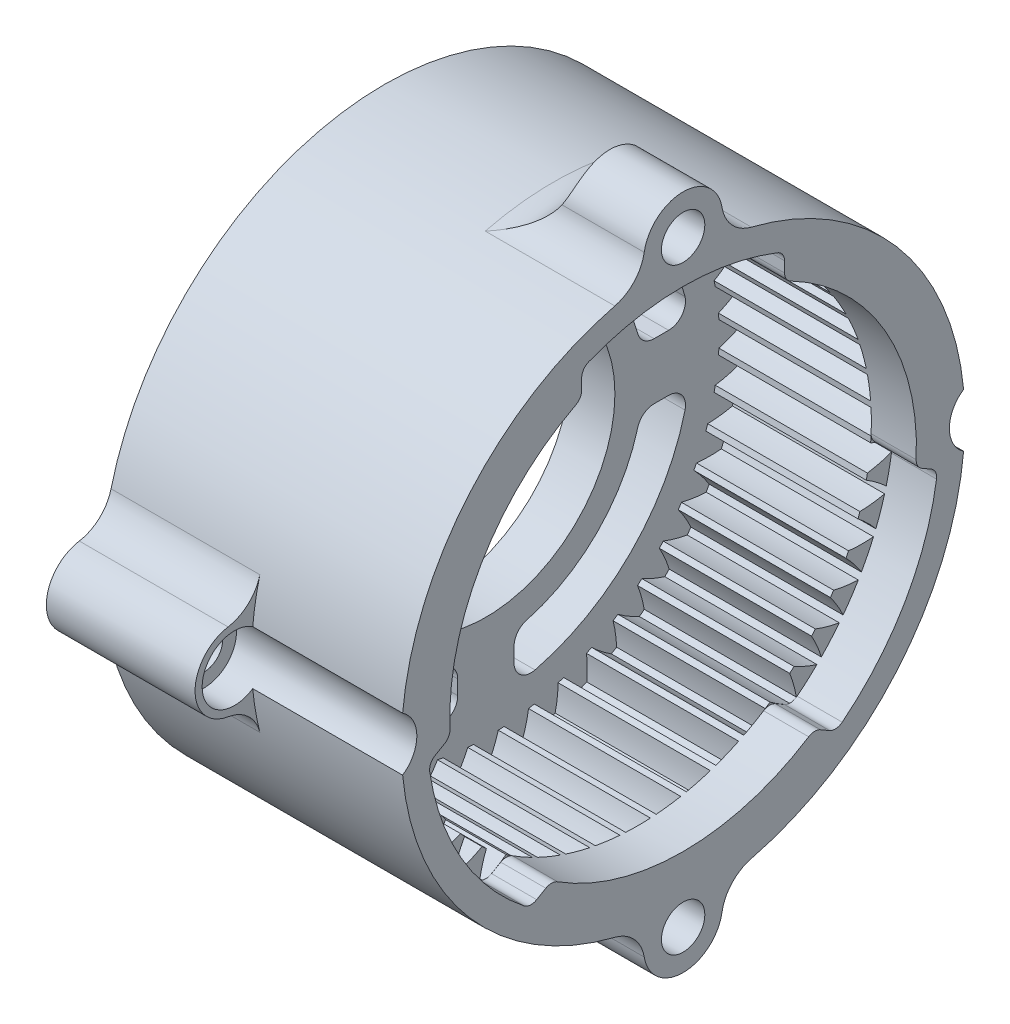
SolidWorks part; units mm, degrees
other "Markup1"
sketch "Sketch14" plane through (17.5, -30, 30) normal (0.8542, -0.3132, 0.4151) x (-0.0246, -0.8217, -0.5694)
other "Markup2"
sketch "Sketch16" plane through (17.5, -30, 30) normal (0.4906, -0.845, 0.2126) x (0.2236, -0.1138, -0.968)
ref_plane "Plane1" through (0, 0, 0) normal (0, 0, 1) x (1, 0, 0)
ref_plane "Plane2" through (0, 0, 0) normal (0, 1, 0) x (1, 0, 0)
ref_plane "Plane3" through (0, 0, 0) normal (1, 0, 0) x (0, 0, -1)
other "Configuration Table"
sketch "HoldingSke" plane through (0, 0, 0) normal (0, 1, 0) x (1, 0, 0)
  line L0 (0, 0) -> (0.7435, -0.8257)
  line L1 (-15, 0) -> (100, 0) construction
  line L2 (0, 0) -> (-2.1039, 2.3779)
  line L3 (0, 0) -> (-11.863, 4.5341)
  line L4 (0, 0) -> (5.7786, 6.4178)
  line L5 (0, 0) -> (-23.7986, -8.8762)
  line L6 (0, 0) -> (-10.5278, -7.1032)
  line L7 (-2.1039, 2.3779) -> (3.3635, 27.1825)
  line L8 (-76.2, 3.2779) -> (-54.61, 3.2779)
  line L9 (-71.009, 38.7566) -> (-53.1078, 45.2721)
  line L10 (-76.2, 71.12) -> (104.1128, 71.12)
  line L11 (0, 0) -> (-12, 0)
  line L12 (-76.2, 101.6) -> (-76.166, 101.6)
  line L13 (24.9733, 27.94) -> (52.9518, 28.4284)
  line L14 (24.9733, 27.94) -> (24.9743, 27.94)
  line L15 (24.9733, 27.94) -> (100.4006, 29.5858)
  circle A0 centre (0, 0) radius 25
  circle A1 centre (0, 0) radius 12.7
  circle A2 centre (0, 0) radius 12.7
  dimension "MHD" = 25.4
  dimension "Hub_dia" = 25.4
  dimension "Diameter" = 50
  dimension "Num_teeth" = 48
  dimension "Pitch" = 1.1111
  dimension "Overall_len" = 25.4
  dimension "Show_teeth" = 48
  dimension "Thickness" = 12.7
  dimension "OAL" = 25.4001
  dimension "T_dim" = 21.59
  dimension "Ap" = 20
  dimension "H" = 19.05
  dimension "Pitch_radius" = 180.3128
  dimension "Width" = 12
  dimension "Backlash" = 0.034
  dimension "Addendum_fac" = 1
  dimension "Dedendum_fac" = 1.25
  dimension "Clearance_fac" = 0.25
  dimension "Dedendum_add" = 0.001
  dimension "Module" = 0.9
sketch "BasProSke" plane through (0, 0, 0) normal (0, 1, 0) x (1, 0, 0)
  line L0 (-10, 0) -> (60, 0) construction
  line L1 (0, 20.7) -> (0, 25)
  line L2 (0, 20.7) -> (12, 20.7)
  line L3 (12, 20.7) -> (12, 25)
  line L4 (12, 25) -> (0, 25)
  dimension "Diameter" = 50
  dimension "Thickness" = 12
  dimension "Inside_diameter" = 41.4
revolve "Base-Revolve" add sketch "BasProSke" angle 360 about L0
sketch "TooCutSke" plane through (0, 0, 0) normal (1, 0, 0) x (0, 0, -1)
  line L3 (0.7917, 21.5855) -> (0.7917, 53.6633) construction
  line L4 (0, 0) -> (0, 59.563) construction
  line L5 (0, 0) -> (-4.4688, 68.1812) construction
  line L6 (-9.2845, 17.6983) -> (36.567, 20.7035) construction
  circle A0 centre (0, 0) radius 21.6 construction
  circle A1 centre (0, 0) radius 22.726 construction
  circle A2 centre (0, 0) radius 18.2676 construction
  circle A3 centre (0, 0) radius 20.6746 construction
  arc A4 (1.1058, 20.645) -> (0.2748, 22.7243) centre (-9.2845, 17.6983) ccw
  arc A5 (1.1058, 20.645) -> (-1.1058, 20.645) centre (0, 0) ccw
  arc A6 (0.2748, 22.7243) -> (-0.2748, 22.7243) centre (0, 0) ccw
  arc A7 (-0.2748, 22.7243) -> (-1.1058, 20.645) centre (9.2845, 17.6983) ccw
  dimension "Pitch_dia" = 43.2
  dimension "Base_dia" = 36.5352
  dimension "Root_dia" = 45.452
  dimension "Overcut_dia" = 41.3492
  dimension "Flank_rad" = 10.8
  dimension "Half_ang" = 3.75
  dimension "Half_CT" = 0.7917
extrude "ToothCut" cut sketch "TooCutSke" along normal through all
fillet "Breaks" [suppressed] radius 0.09
fillet "RootFillets" [suppressed] radius 0.226
pattern_circular "TeethCuts" count 48 every 7.5 about axis through (-10, 0, 0) along (1, 0, 0) of "RootFillets", "Breaks", "ToothCut"
sketch "Sketch1" plane through (0, 0, 0) normal (-1, 0, 0) x (0, 0, 1)
  circle A0 centre (0, 0) radius 25
  circle A1 centre (0, 0) radius 25 construction
  circle A2 centre (0, 0) radius 11.45
  dimension "D1" = 22.9
extrude "Boss-Extrude1" add sketch "Sketch1" along normal blind 9
ref_plane "Plane4" through (1.5, 0, 0) normal (-1, 0, 0) x (0, 0, 1)
sketch "Sketch2" plane through (1.5, 0, 0) normal (-1, 0, 0) x (0, 0, 1)
  line L0 (-26.5, 0) -> (0, 0) construction
  line L1 (0, 11.45) -> (0, -11.45) construction
  line L2 (-26.5, 3.5) -> (-24.7538, 3.5)
  line L3 (-26.5, -3.5) -> (-24.7538, -3.5)
  line L4 (26.5, 3.5) -> (24.7538, 3.5)
  line L5 (26.5, -3.5) -> (24.7538, -3.5)
  arc A0 (-26.5, 3.5) -> (-26.5, -3.5) centre (-26.5, 0) ccw
  circle A1 centre (0, 0) radius 25 construction
  arc A2 (-24.7538, 3.5) -> (-24.7538, -3.5) centre (0, 0) ccw
  circle A3 centre (0, 0) radius 11.45 construction
  arc A4 (24.7538, 3.5) -> (24.7538, -3.5) centre (0, 0) cw
  arc A5 (26.5, 3.5) -> (26.5, -3.5) centre (26.5, 0) cw
  point P12 (0, 0)
  dimension "D2" = 7
  dimension "D1" = 26.5
extrude "Boss-Extrude2" add sketch "Sketch2" along normal up to surface (10.5 mm away) up to face at (-9, 0, 25)
sketch "Sketch3" plane through (1.5, 0, 0) normal (1, 0, 0) x (0, 0, -1)
  circle A0 centre (-26.5, 0) radius 1.65
  circle A1 centre (26.5, 0) radius 1.65
  arc A2 (26.5, -3.5) -> (26.5, 3.5) centre (26.5, 0) ccw construction
  arc A4 (-26.5, 3.5) -> (-26.5, -3.5) centre (-26.5, 0) ccw construction
  dimension "D1" = 3.3
extrude "Cut-Extrude1" cut sketch "Sketch3" against normal up to surface (10.5 mm away) up to face at (-9, 0, 0)
sketch "Sketch4" plane through (1.5, 0, 0) normal (1, 0, 0) x (0, 0, -1)
  line L0 (0, 11.45) -> (0, -11.45) construction
  circle A1 centre (26.5, 0) radius 2.875
  arc A2 (26.5, -3.5) -> (26.5, 3.5) centre (26.5, 0) ccw construction
  circle A3 centre (0, 0) radius 11.45 construction
  circle A4 centre (-26.5, 0) radius 2.875
  point P12 (0, 0)
  dimension "D1" = 5.75
extrude "Cut-Extrude2" cut sketch "Sketch4" along normal through all
sketch "Sketch5" plane through (1.5, 0, 0) normal (1, 0, 0) x (0, 0, -1)
  line L0 (0, 11.45) -> (0, -11.45) construction
  line L1 (-24.7538, -3.5) -> (-26.5, -3.5)
  line L2 (24.7538, -3.5) -> (26.5, -3.5)
  line L3 (26.5, 3.5) -> (24.7538, 3.5)
  line L4 (24.7538, -3.5) -> (26.5, -3.5)
  line L5 (26.5, 3.5) -> (24.7538, 3.5)
  line L6 (-26.5, 3.5) -> (-24.7538, 3.5)
  arc A0 (24.8865, -2.3795) -> (24.8865, 2.3795) centre (26.5, 0) ccw
  arc A1 (26.5, -3.5) -> (26.5, 3.5) centre (26.5, 0) ccw construction
  circle A3 centre (0, 0) radius 11.45 construction
  arc A4 (-24.8865, -2.3795) -> (-24.8865, 2.3795) centre (-26.5, 0) cw
  arc A5 (-24.7538, -3.5) -> (-24.8865, -2.3795) centre (0, 0) cw
  arc A6 (-26.5, -3.5) -> (-26.5, 3.5) centre (-26.5, 0) cw
  arc A7 (24.8865, 2.3795) -> (24.7538, 3.5) centre (0, 0) ccw
  arc A10 (26.5, -3.5) -> (26.5, 3.5) centre (26.5, 0) ccw
  arc A14 (26.5, -3.5) -> (26.5, 3.5) centre (26.5, 0) ccw
  arc A15 (-24.8865, 2.3795) -> (-24.7538, 3.5) centre (0, 0) cw
  arc A19 (24.8865, 2.3795) -> (24.7538, 3.5) centre (0, 0) ccw
  arc A21 (24.8865, 2.3795) -> (24.8865, -2.3795) centre (26.5, 0) ccw
  arc A23 (24.7538, -3.5) -> (24.8865, -2.3795) centre (0, 0) ccw
  arc A24 (24.7538, -3.5) -> (24.8865, -2.3795) centre (0, 0) ccw
  point P19 (0, 0)
  dimension "D1" = 2.875
  dimension "D2" = 0
extrude "Boss-Extrude3" add sketch "Sketch5" along normal blind 2.7
sketch "Sketch8" plane through (-9, 0, 0) normal (-1, 0, 0) x (0, 0, 1)
  circle A0 centre (0, 0) radius 20.7
  arc A1 (20.3506, 3.7871) -> (20.2508, 4.289) centre (0, 0) ccw construction
extrude "Cut-Extrude4" cut sketch "Sketch8" against normal blind 5 and the other way through all
fillet "Fillet1" radius 3.5 4 edges at (-2.4, 3.5, -24.7538) (-2.4, -3.5, -24.7538) (-2.4, -3.5, 24.7538) (-2.4, 3.5, 24.7538)
sketch "Sketch15" plane through (12, 0, 0) normal (1, 0, 0) x (0, 0, -1)
  arc A12 (24.8865, 2.3795) -> (24.8865, -2.3795) centre (26.5, 0) ccw construction
  arc A13 (24.8865, 2.3795) -> (-24.8865, 2.3795) centre (0, 0) ccw construction
  arc A14 (-24.8865, -2.3795) -> (-24.8865, 2.3795) centre (-26.5, 0) ccw construction
  arc A15 (-24.8865, -2.3795) -> (24.8865, -2.3795) centre (0, 0) ccw construction
  arc A16 (-3.2385, -22.4941) -> (-2.6937, -22.5658) centre (0, 0) ccw construction
  arc A17 (-2.6937, -22.5658) -> (-1.6091, -20.6374) centre (-11.5151, -16.335) ccw construction
  arc A18 (-1.6091, -20.6374) -> (-1.0984, -20.6708) centre (0, 0) ccw construction
  arc A19 (-1.0984, -20.6708) -> (-0.2748, -22.7243) centre (9.2845, -17.6983) ccw construction
  arc A20 (-0.2748, -22.7243) -> (0.2748, -22.7243) centre (0, 0) ccw construction
  arc A21 (0.2748, -22.7243) -> (1.0984, -20.6708) centre (-9.2845, -17.6983) ccw construction
  arc A22 (1.0984, -20.6708) -> (1.6091, -20.6374) centre (0, 0) ccw construction
  arc A23 (1.6091, -20.6374) -> (2.6937, -22.5658) centre (11.5151, -16.335) ccw construction
  arc A24 (2.6937, -22.5658) -> (3.2385, -22.4941) centre (0, 0) ccw construction
  arc A25 (3.2385, -22.4941) -> (3.7871, -20.3506) centre (-6.8949, -18.7587) ccw construction
  arc A26 (3.7871, -20.3506) -> (4.289, -20.2508) centre (0, 0) ccw construction
  arc A27 (4.289, -20.2508) -> (5.6161, -22.0211) centre (13.5488, -14.6922) ccw construction
  arc A28 (5.6161, -22.0211) -> (6.1469, -21.8789) centre (0, 0) ccw construction
  arc A29 (6.1469, -21.8789) -> (6.411, -19.6822) centre (-4.3874, -19.4982) ccw construction
  arc A30 (6.411, -19.6822) -> (6.8956, -19.5177) centre (0, 0) ccw construction
  arc A31 (6.8956, -19.5177) -> (8.4424, -21.0997) centre (15.3506, -12.7981) ccw construction
  arc A32 (8.4424, -21.0997) -> (8.9501, -20.8894) centre (0, 0) ccw construction
  arc A33 (8.9501, -20.8894) -> (8.9252, -18.677) centre (-1.8049, -19.9041) ccw construction
  arc A34 (8.9252, -18.677) -> (9.3842, -18.4507) centre (0, 0) ccw construction
  arc A35 (9.3842, -18.4507) -> (11.1242, -19.8172) centre (16.8897, -10.6849) ccw construction
  arc A36 (11.1242, -19.8172) -> (11.6001, -19.5425) centre (0, 0) ccw construction
  arc A37 (11.6001, -19.5425) -> (11.2867, -17.3523) centre (0.8086, -19.9694) ccw construction
  arc A38 (11.2867, -17.3523) -> (11.7122, -17.0679) centre (0, 0) ccw construction
  arc A39 (11.7122, -17.0679) -> (13.6157, -18.1957) centre (18.1399, -8.389) ccw construction
  arc A40 (13.6157, -18.1957) -> (14.0517, -17.8612) centre (0, 0) ccw construction
  arc A41 (14.0517, -17.8612) -> (13.455, -15.7306) centre (3.4082, -19.693) ccw construction
  arc A42 (13.455, -15.7306) -> (13.8398, -15.3932) centre (0, 0) ccw construction
  arc A43 (13.8398, -15.3932) -> (15.8742, -16.2628) centre (19.0797, -5.9495) ccw construction
  arc A44 (15.8742, -16.2628) -> (16.2628, -15.8742) centre (0, 0) ccw construction
  arc A45 (16.2628, -15.8742) -> (15.3932, -13.8398) centre (5.9495, -19.0797) ccw construction
  arc A46 (15.3932, -13.8398) -> (15.7306, -13.455) centre (0, 0) ccw construction
  arc A47 (15.7306, -13.455) -> (17.8612, -14.0517) centre (19.693, -3.4082) ccw construction
  arc A48 (17.8612, -14.0517) -> (18.1957, -13.6157) centre (0, 0) ccw construction
  arc A49 (18.1957, -13.6157) -> (17.0679, -11.7122) centre (8.389, -18.1399) ccw construction
  arc A50 (17.0679, -11.7122) -> (17.3523, -11.2867) centre (0, 0) ccw construction
  arc A51 (17.3523, -11.2867) -> (19.5425, -11.6001) centre (19.9694, -0.8086) ccw construction
  arc A52 (19.5425, -11.6001) -> (19.8172, -11.1242) centre (0, 0) ccw construction
  arc A53 (19.8172, -11.1242) -> (18.4507, -9.3842) centre (10.6849, -16.8897) ccw construction
  arc A54 (18.4507, -9.3842) -> (18.677, -8.9252) centre (0, 0) ccw construction
  arc A55 (18.677, -8.9252) -> (20.8894, -8.9501) centre (19.9041, 1.8049) ccw construction
  arc A56 (20.8894, -8.9501) -> (21.0997, -8.4424) centre (0, 0) ccw construction
  arc A57 (21.0997, -8.4424) -> (19.5177, -6.8956) centre (12.7981, -15.3506) ccw construction
  arc A58 (19.5177, -6.8956) -> (19.6822, -6.411) centre (0, 0) ccw construction
  arc A59 (19.6822, -6.411) -> (21.8789, -6.1469) centre (19.4982, 4.3874) ccw construction
  arc A60 (21.8789, -6.1469) -> (22.0211, -5.6161) centre (0, 0) ccw construction
  arc A61 (22.0211, -5.6161) -> (20.2508, -4.289) centre (14.6922, -13.5488) ccw construction
  arc A62 (20.2508, -4.289) -> (20.3506, -3.7871) centre (0, 0) ccw construction
  arc A63 (20.3506, -3.7871) -> (22.4941, -3.2385) centre (18.7587, 6.8949) ccw construction
  arc A64 (22.4941, -3.2385) -> (22.5658, -2.6937) centre (0, 0) ccw construction
  arc A65 (22.5658, -2.6937) -> (20.6374, -1.6091) centre (16.335, -11.5151) ccw construction
  arc A66 (20.6374, -1.6091) -> (20.6708, -1.0984) centre (0, 0) ccw construction
  arc A67 (20.6708, -1.0984) -> (22.7243, -0.2748) centre (17.6983, 9.2845) ccw construction
  arc A68 (22.7243, -0.2748) -> (22.7243, 0.2748) centre (0, 0) ccw construction
  arc A69 (22.7243, 0.2748) -> (20.6708, 1.0984) centre (17.6983, -9.2845) ccw construction
  arc A70 (20.6708, 1.0984) -> (20.6374, 1.6091) centre (0, 0) ccw construction
  arc A71 (20.6374, 1.6091) -> (22.5658, 2.6937) centre (16.335, 11.5151) ccw construction
  arc A72 (22.5658, 2.6937) -> (22.4941, 3.2385) centre (0, 0) ccw construction
  arc A73 (22.4941, 3.2385) -> (20.3506, 3.7871) centre (18.7587, -6.8949) ccw construction
  arc A74 (20.3506, 3.7871) -> (20.2508, 4.289) centre (0, 0) ccw construction
  arc A75 (20.2508, 4.289) -> (22.0211, 5.6161) centre (14.6922, 13.5488) ccw construction
  arc A76 (22.0211, 5.6161) -> (21.8789, 6.1469) centre (0, 0) ccw construction
  arc A77 (21.8789, 6.1469) -> (19.6822, 6.411) centre (19.4982, -4.3874) ccw construction
  arc A78 (19.6822, 6.411) -> (19.5177, 6.8956) centre (0, 0) ccw construction
  arc A79 (19.5177, 6.8956) -> (21.0997, 8.4424) centre (12.7981, 15.3506) ccw construction
  arc A80 (21.0997, 8.4424) -> (20.8894, 8.9501) centre (0, 0) ccw construction
  arc A81 (20.8894, 8.9501) -> (18.677, 8.9252) centre (19.9041, -1.8049) ccw construction
  arc A82 (18.677, 8.9252) -> (18.4507, 9.3842) centre (0, 0) ccw construction
  arc A83 (18.4507, 9.3842) -> (19.8172, 11.1242) centre (10.6849, 16.8897) ccw construction
  arc A84 (19.8172, 11.1242) -> (19.5425, 11.6001) centre (0, 0) ccw construction
  arc A85 (19.5425, 11.6001) -> (17.3523, 11.2867) centre (19.9694, 0.8086) ccw construction
  arc A86 (17.3523, 11.2867) -> (17.0679, 11.7122) centre (0, 0) ccw construction
  arc A87 (17.0679, 11.7122) -> (18.1957, 13.6157) centre (8.389, 18.1399) ccw construction
  arc A88 (18.1957, 13.6157) -> (17.8612, 14.0517) centre (0, 0) ccw construction
  arc A89 (17.8612, 14.0517) -> (15.7306, 13.455) centre (19.693, 3.4082) ccw construction
  arc A90 (15.7306, 13.455) -> (15.3932, 13.8398) centre (0, 0) ccw construction
  arc A91 (15.3932, 13.8398) -> (16.2628, 15.8742) centre (5.9495, 19.0797) ccw construction
  arc A92 (16.2628, 15.8742) -> (15.8742, 16.2628) centre (0, 0) ccw construction
  arc A93 (15.8742, 16.2628) -> (13.8398, 15.3932) centre (19.0797, 5.9495) ccw construction
  arc A94 (13.8398, 15.3932) -> (13.455, 15.7306) centre (0, 0) ccw construction
  arc A95 (13.455, 15.7306) -> (14.0517, 17.8612) centre (3.4082, 19.693) ccw construction
  arc A96 (14.0517, 17.8612) -> (13.6157, 18.1957) centre (0, 0) ccw construction
  arc A97 (13.6157, 18.1957) -> (11.7122, 17.0679) centre (18.1399, 8.389) ccw construction
  arc A98 (11.7122, 17.0679) -> (11.2867, 17.3523) centre (0, 0) ccw construction
  arc A99 (11.2867, 17.3523) -> (11.6001, 19.5425) centre (0.8086, 19.9694) ccw construction
  arc A100 (11.6001, 19.5425) -> (11.1242, 19.8172) centre (0, 0) ccw construction
  arc A101 (11.1242, 19.8172) -> (9.3842, 18.4507) centre (16.8897, 10.6849) ccw construction
  arc A102 (9.3842, 18.4507) -> (8.9252, 18.677) centre (0, 0) ccw construction
  arc A103 (8.9252, 18.677) -> (8.9501, 20.8894) centre (-1.8049, 19.9041) ccw construction
  arc A104 (8.9501, 20.8894) -> (8.4424, 21.0997) centre (0, 0) ccw construction
  arc A105 (8.4424, 21.0997) -> (6.8956, 19.5177) centre (15.3506, 12.7981) ccw construction
  arc A106 (6.8956, 19.5177) -> (6.411, 19.6822) centre (0, 0) ccw construction
  arc A107 (6.411, 19.6822) -> (6.1469, 21.8789) centre (-4.3874, 19.4982) ccw construction
  arc A108 (6.1469, 21.8789) -> (5.6161, 22.0211) centre (0, 0) ccw construction
  arc A109 (5.6161, 22.0211) -> (4.289, 20.2508) centre (13.5488, 14.6922) ccw construction
  arc A110 (4.289, 20.2508) -> (3.7871, 20.3506) centre (0, 0) ccw construction
  arc A111 (3.7871, 20.3506) -> (3.2385, 22.4941) centre (-6.8949, 18.7587) ccw construction
  arc A112 (3.2385, 22.4941) -> (2.6937, 22.5658) centre (0, 0) ccw construction
  arc A113 (2.6937, 22.5658) -> (1.6091, 20.6374) centre (11.5151, 16.335) ccw construction
  arc A114 (1.6091, 20.6374) -> (1.0984, 20.6708) centre (0, 0) ccw construction
  arc A115 (1.0984, 20.6708) -> (0.2748, 22.7243) centre (-9.2845, 17.6983) ccw construction
  arc A116 (0.2748, 22.7243) -> (-0.2748, 22.7243) centre (0, 0) ccw construction
  arc A117 (-0.2748, 22.7243) -> (-1.0984, 20.6708) centre (9.2845, 17.6983) ccw construction
  arc A118 (-1.0984, 20.6708) -> (-1.6091, 20.6374) centre (0, 0) ccw construction
  arc A119 (-1.6091, 20.6374) -> (-2.6937, 22.5658) centre (-11.5151, 16.335) ccw construction
  arc A120 (-2.6937, 22.5658) -> (-3.2385, 22.4941) centre (0, 0) ccw construction
  arc A121 (-3.2385, 22.4941) -> (-3.7871, 20.3506) centre (6.8949, 18.7587) ccw construction
  arc A122 (-3.7871, 20.3506) -> (-4.289, 20.2508) centre (0, 0) ccw construction
  arc A123 (-4.289, 20.2508) -> (-5.6161, 22.0211) centre (-13.5488, 14.6922) ccw construction
  arc A124 (-5.6161, 22.0211) -> (-6.1469, 21.8789) centre (0, 0) ccw construction
  arc A125 (-6.1469, 21.8789) -> (-6.411, 19.6822) centre (4.3874, 19.4982) ccw construction
  arc A126 (-6.411, 19.6822) -> (-6.8956, 19.5177) centre (0, 0) ccw construction
  arc A127 (-6.8956, 19.5177) -> (-8.4424, 21.0997) centre (-15.3506, 12.7981) ccw construction
  arc A128 (-8.4424, 21.0997) -> (-8.9501, 20.8894) centre (0, 0) ccw construction
  arc A129 (-8.9501, 20.8894) -> (-8.9252, 18.677) centre (1.8049, 19.9041) ccw construction
  arc A130 (-8.9252, 18.677) -> (-9.3842, 18.4507) centre (0, 0) ccw construction
  arc A131 (-9.3842, 18.4507) -> (-11.1242, 19.8172) centre (-16.8897, 10.6849) ccw construction
  arc A132 (-11.1242, 19.8172) -> (-11.6001, 19.5425) centre (0, 0) ccw construction
  arc A133 (-11.6001, 19.5425) -> (-11.2867, 17.3523) centre (-0.8086, 19.9694) ccw construction
  arc A134 (-11.2867, 17.3523) -> (-11.7122, 17.0679) centre (0, 0) ccw construction
  arc A135 (-11.7122, 17.0679) -> (-13.6157, 18.1957) centre (-18.1399, 8.389) ccw construction
  arc A136 (-13.6157, 18.1957) -> (-14.0517, 17.8612) centre (0, 0) ccw construction
  arc A137 (-14.0517, 17.8612) -> (-13.455, 15.7306) centre (-3.4082, 19.693) ccw construction
  arc A138 (-13.455, 15.7306) -> (-13.8398, 15.3932) centre (0, 0) ccw construction
  arc A139 (-13.8398, 15.3932) -> (-15.8742, 16.2628) centre (-19.0797, 5.9495) ccw construction
  arc A140 (-15.8742, 16.2628) -> (-16.2628, 15.8742) centre (0, 0) ccw construction
  arc A141 (-16.2628, 15.8742) -> (-15.3932, 13.8398) centre (-5.9495, 19.0797) ccw construction
  arc A142 (-15.3932, 13.8398) -> (-15.7306, 13.455) centre (0, 0) ccw construction
  arc A143 (-15.7306, 13.455) -> (-17.8612, 14.0517) centre (-19.693, 3.4082) ccw construction
  arc A144 (-17.8612, 14.0517) -> (-18.1957, 13.6157) centre (0, 0) ccw construction
  arc A145 (-18.1957, 13.6157) -> (-17.0679, 11.7122) centre (-8.389, 18.1399) ccw construction
  arc A146 (-17.0679, 11.7122) -> (-17.3523, 11.2867) centre (0, 0) ccw construction
  arc A147 (-17.3523, 11.2867) -> (-19.5425, 11.6001) centre (-19.9694, 0.8086) ccw construction
  arc A148 (-19.5425, 11.6001) -> (-19.8172, 11.1242) centre (0, 0) ccw construction
  arc A149 (-19.8172, 11.1242) -> (-18.4507, 9.3842) centre (-10.6849, 16.8897) ccw construction
  arc A150 (-18.4507, 9.3842) -> (-18.677, 8.9252) centre (0, 0) ccw construction
  arc A151 (-18.677, 8.9252) -> (-20.8894, 8.9501) centre (-19.9041, -1.8049) ccw construction
  arc A152 (-20.8894, 8.9501) -> (-21.0997, 8.4424) centre (0, 0) ccw construction
  arc A153 (-21.0997, 8.4424) -> (-19.5177, 6.8956) centre (-12.7981, 15.3506) ccw construction
  arc A154 (-19.5177, 6.8956) -> (-19.6822, 6.411) centre (0, 0) ccw construction
  arc A155 (-19.6822, 6.411) -> (-21.8789, 6.1469) centre (-19.4982, -4.3874) ccw construction
  arc A156 (-21.8789, 6.1469) -> (-22.0211, 5.6161) centre (0, 0) ccw construction
  arc A157 (-22.0211, 5.6161) -> (-20.2508, 4.289) centre (-14.6922, 13.5488) ccw construction
  arc A158 (-20.2508, 4.289) -> (-20.3506, 3.7871) centre (0, 0) ccw construction
  arc A159 (-20.3506, 3.7871) -> (-22.4941, 3.2385) centre (-18.7587, -6.8949) ccw construction
  arc A160 (-22.4941, 3.2385) -> (-22.5658, 2.6937) centre (0, 0) ccw construction
  arc A161 (-22.5658, 2.6937) -> (-20.6374, 1.6091) centre (-16.335, 11.5151) ccw construction
  arc A162 (-20.6374, 1.6091) -> (-20.6708, 1.0984) centre (0, 0) ccw construction
  arc A163 (-20.6708, 1.0984) -> (-22.7243, 0.2748) centre (-17.6983, -9.2845) ccw construction
  arc A164 (-22.7243, 0.2748) -> (-22.7243, -0.2748) centre (0, 0) ccw construction
  arc A165 (-22.7243, -0.2748) -> (-20.6708, -1.0984) centre (-17.6983, 9.2845) ccw construction
  arc A166 (-20.6708, -1.0984) -> (-20.6374, -1.6091) centre (0, 0) ccw construction
  arc A167 (-20.6374, -1.6091) -> (-22.5658, -2.6937) centre (-16.335, -11.5151) ccw construction
  arc A168 (-22.5658, -2.6937) -> (-22.4941, -3.2385) centre (0, 0) ccw construction
  arc A169 (-22.4941, -3.2385) -> (-20.3506, -3.7871) centre (-18.7587, 6.8949) ccw construction
  arc A170 (-20.3506, -3.7871) -> (-20.2508, -4.289) centre (0, 0) ccw construction
  arc A171 (-20.2508, -4.289) -> (-22.0211, -5.6161) centre (-14.6922, -13.5488) ccw construction
  arc A172 (-22.0211, -5.6161) -> (-21.8789, -6.1469) centre (0, 0) ccw construction
  arc A173 (-21.8789, -6.1469) -> (-19.6822, -6.411) centre (-19.4982, 4.3874) ccw construction
  arc A174 (-19.6822, -6.411) -> (-19.5177, -6.8956) centre (0, 0) ccw construction
  arc A175 (-19.5177, -6.8956) -> (-21.0997, -8.4424) centre (-12.7981, -15.3506) ccw construction
  arc A176 (-21.0997, -8.4424) -> (-20.8894, -8.9501) centre (0, 0) ccw construction
  arc A177 (-20.8894, -8.9501) -> (-18.677, -8.9252) centre (-19.9041, 1.8049) ccw construction
  arc A178 (-18.677, -8.9252) -> (-18.4507, -9.3842) centre (0, 0) ccw construction
  arc A179 (-18.4507, -9.3842) -> (-19.8172, -11.1242) centre (-10.6849, -16.8897) ccw construction
  arc A180 (-19.8172, -11.1242) -> (-19.5425, -11.6001) centre (0, 0) ccw construction
  arc A181 (-19.5425, -11.6001) -> (-17.3523, -11.2867) centre (-19.9694, -0.8086) ccw construction
  arc A182 (-17.3523, -11.2867) -> (-17.0679, -11.7122) centre (0, 0) ccw construction
  arc A183 (-17.0679, -11.7122) -> (-18.1957, -13.6157) centre (-8.389, -18.1399) ccw construction
  arc A184 (-18.1957, -13.6157) -> (-17.8612, -14.0517) centre (0, 0) ccw construction
  arc A185 (-17.8612, -14.0517) -> (-15.7306, -13.455) centre (-19.693, -3.4082) ccw construction
  arc A186 (-15.7306, -13.455) -> (-15.3932, -13.8398) centre (0, 0) ccw construction
  arc A187 (-15.3932, -13.8398) -> (-16.2628, -15.8742) centre (-5.9495, -19.0797) ccw construction
  arc A188 (-16.2628, -15.8742) -> (-15.8742, -16.2628) centre (0, 0) ccw construction
  arc A189 (-15.8742, -16.2628) -> (-13.8398, -15.3932) centre (-19.0797, -5.9495) ccw construction
  arc A190 (-13.8398, -15.3932) -> (-13.455, -15.7306) centre (0, 0) ccw construction
  arc A191 (-13.455, -15.7306) -> (-14.0517, -17.8612) centre (-3.4082, -19.693) ccw construction
  arc A192 (-14.0517, -17.8612) -> (-13.6157, -18.1957) centre (0, 0) ccw construction
  arc A193 (-13.6157, -18.1957) -> (-11.7122, -17.0679) centre (-18.1399, -8.389) ccw construction
  arc A194 (-11.7122, -17.0679) -> (-11.2867, -17.3523) centre (0, 0) ccw construction
  arc A195 (-11.2867, -17.3523) -> (-11.6001, -19.5425) centre (-0.8086, -19.9694) ccw construction
  arc A196 (-11.6001, -19.5425) -> (-11.1242, -19.8172) centre (0, 0) ccw construction
  arc A197 (-11.1242, -19.8172) -> (-9.3842, -18.4507) centre (-16.8897, -10.6849) ccw construction
  arc A198 (-9.3842, -18.4507) -> (-8.9252, -18.677) centre (0, 0) ccw construction
  arc A199 (-8.9252, -18.677) -> (-8.9501, -20.8894) centre (1.8049, -19.9041) ccw construction
  arc A200 (-8.9501, -20.8894) -> (-8.4424, -21.0997) centre (0, 0) ccw construction
  arc A201 (-8.4424, -21.0997) -> (-6.8956, -19.5177) centre (-15.3506, -12.7981) ccw construction
  arc A202 (-6.8956, -19.5177) -> (-6.411, -19.6822) centre (0, 0) ccw construction
  arc A203 (-6.411, -19.6822) -> (-6.1469, -21.8789) centre (4.3874, -19.4982) ccw construction
  arc A204 (-6.1469, -21.8789) -> (-5.6161, -22.0211) centre (0, 0) ccw construction
  arc A205 (-5.6161, -22.0211) -> (-4.289, -20.2508) centre (-13.5488, -14.6922) ccw construction
  arc A206 (-4.289, -20.2508) -> (-3.7871, -20.3506) centre (0, 0) ccw construction
  arc A207 (-3.7871, -20.3506) -> (-3.2385, -22.4941) centre (6.8949, -18.7587) ccw construction
  arc A208 (24.8865, 2.3795) -> (24.8865, -2.3795) centre (26.5, 0) ccw
  arc A209 (24.8865, 2.3795) -> (-24.8865, 2.3795) centre (0, 0) ccw
  arc A210 (-24.8865, -2.3795) -> (-24.8865, 2.3795) centre (-26.5, 0) ccw
  arc A211 (-24.8865, -2.3795) -> (24.8865, -2.3795) centre (0, 0) ccw
  arc A212 (-3.2385, -22.4941) -> (-2.6937, -22.5658) centre (0, 0) ccw
  arc A213 (-2.6937, -22.5658) -> (-1.6091, -20.6374) centre (-11.5151, -16.335) ccw
  arc A214 (-1.6091, -20.6374) -> (-1.0984, -20.6708) centre (0, 0) ccw
  arc A215 (-1.0984, -20.6708) -> (-0.2748, -22.7243) centre (9.2845, -17.6983) ccw
  arc A216 (-0.2748, -22.7243) -> (0.2748, -22.7243) centre (0, 0) ccw
  arc A217 (0.2748, -22.7243) -> (1.0984, -20.6708) centre (-9.2845, -17.6983) ccw
  arc A218 (1.0984, -20.6708) -> (1.6091, -20.6374) centre (0, 0) ccw
  arc A219 (1.6091, -20.6374) -> (2.6937, -22.5658) centre (11.5151, -16.335) ccw
  arc A220 (2.6937, -22.5658) -> (3.2385, -22.4941) centre (0, 0) ccw
  arc A221 (3.2385, -22.4941) -> (3.7871, -20.3506) centre (-6.8949, -18.7587) ccw
  arc A222 (3.7871, -20.3506) -> (4.289, -20.2508) centre (0, 0) ccw
  arc A223 (4.289, -20.2508) -> (5.6161, -22.0211) centre (13.5488, -14.6922) ccw
  arc A224 (5.6161, -22.0211) -> (6.1469, -21.8789) centre (0, 0) ccw
  arc A225 (6.1469, -21.8789) -> (6.411, -19.6822) centre (-4.3874, -19.4982) ccw
  arc A226 (6.411, -19.6822) -> (6.8956, -19.5177) centre (0, 0) ccw
  arc A227 (6.8956, -19.5177) -> (8.4424, -21.0997) centre (15.3506, -12.7981) ccw
  arc A228 (8.4424, -21.0997) -> (8.9501, -20.8894) centre (0, 0) ccw
  arc A229 (8.9501, -20.8894) -> (8.9252, -18.677) centre (-1.8049, -19.9041) ccw
  arc A230 (8.9252, -18.677) -> (9.3842, -18.4507) centre (0, 0) ccw
  arc A231 (9.3842, -18.4507) -> (11.1242, -19.8172) centre (16.8897, -10.6849) ccw
  arc A232 (11.1242, -19.8172) -> (11.6001, -19.5425) centre (0, 0) ccw
  arc A233 (11.6001, -19.5425) -> (11.2867, -17.3523) centre (0.8086, -19.9694) ccw
  arc A234 (11.2867, -17.3523) -> (11.7122, -17.0679) centre (0, 0) ccw
  arc A235 (11.7122, -17.0679) -> (13.6157, -18.1957) centre (18.1399, -8.389) ccw
  arc A236 (13.6157, -18.1957) -> (14.0517, -17.8612) centre (0, 0) ccw
  arc A237 (14.0517, -17.8612) -> (13.455, -15.7306) centre (3.4082, -19.693) ccw
  arc A238 (13.455, -15.7306) -> (13.8398, -15.3932) centre (0, 0) ccw
  arc A239 (13.8398, -15.3932) -> (15.8742, -16.2628) centre (19.0797, -5.9495) ccw
  arc A240 (15.8742, -16.2628) -> (16.2628, -15.8742) centre (0, 0) ccw
  arc A241 (16.2628, -15.8742) -> (15.3932, -13.8398) centre (5.9495, -19.0797) ccw
  arc A242 (15.3932, -13.8398) -> (15.7306, -13.455) centre (0, 0) ccw
  arc A243 (15.7306, -13.455) -> (17.8612, -14.0517) centre (19.693, -3.4082) ccw
  arc A244 (17.8612, -14.0517) -> (18.1957, -13.6157) centre (0, 0) ccw
  arc A245 (18.1957, -13.6157) -> (17.0679, -11.7122) centre (8.389, -18.1399) ccw
  arc A246 (17.0679, -11.7122) -> (17.3523, -11.2867) centre (0, 0) ccw
  arc A247 (17.3523, -11.2867) -> (19.5425, -11.6001) centre (19.9694, -0.8086) ccw
  arc A248 (19.5425, -11.6001) -> (19.8172, -11.1242) centre (0, 0) ccw
  arc A249 (19.8172, -11.1242) -> (18.4507, -9.3842) centre (10.6849, -16.8897) ccw
  arc A250 (18.4507, -9.3842) -> (18.677, -8.9252) centre (0, 0) ccw
  arc A251 (18.677, -8.9252) -> (20.8894, -8.9501) centre (19.9041, 1.8049) ccw
  arc A252 (20.8894, -8.9501) -> (21.0997, -8.4424) centre (0, 0) ccw
  arc A253 (21.0997, -8.4424) -> (19.5177, -6.8956) centre (12.7981, -15.3506) ccw
  arc A254 (19.5177, -6.8956) -> (19.6822, -6.411) centre (0, 0) ccw
  arc A255 (19.6822, -6.411) -> (21.8789, -6.1469) centre (19.4982, 4.3874) ccw
  arc A256 (21.8789, -6.1469) -> (22.0211, -5.6161) centre (0, 0) ccw
  arc A257 (22.0211, -5.6161) -> (20.2508, -4.289) centre (14.6922, -13.5488) ccw
  arc A258 (20.2508, -4.289) -> (20.3506, -3.7871) centre (0, 0) ccw
  arc A259 (20.3506, -3.7871) -> (22.4941, -3.2385) centre (18.7587, 6.8949) ccw
  arc A260 (22.4941, -3.2385) -> (22.5658, -2.6937) centre (0, 0) ccw
  arc A261 (22.5658, -2.6937) -> (20.6374, -1.6091) centre (16.335, -11.5151) ccw
  arc A262 (20.6374, -1.6091) -> (20.6708, -1.0984) centre (0, 0) ccw
  arc A263 (20.6708, -1.0984) -> (22.7243, -0.2748) centre (17.6983, 9.2845) ccw
  arc A264 (22.7243, -0.2748) -> (22.7243, 0.2748) centre (0, 0) ccw
  arc A265 (22.7243, 0.2748) -> (20.6708, 1.0984) centre (17.6983, -9.2845) ccw
  arc A266 (20.6708, 1.0984) -> (20.6374, 1.6091) centre (0, 0) ccw
  arc A267 (20.6374, 1.6091) -> (22.5658, 2.6937) centre (16.335, 11.5151) ccw
  arc A268 (22.5658, 2.6937) -> (22.4941, 3.2385) centre (0, 0) ccw
  arc A269 (22.4941, 3.2385) -> (20.3506, 3.7871) centre (18.7587, -6.8949) ccw
  arc A270 (20.3506, 3.7871) -> (20.2508, 4.289) centre (0, 0) ccw
  arc A271 (20.2508, 4.289) -> (22.0211, 5.6161) centre (14.6922, 13.5488) ccw
  arc A272 (22.0211, 5.6161) -> (21.8789, 6.1469) centre (0, 0) ccw
  arc A273 (21.8789, 6.1469) -> (19.6822, 6.411) centre (19.4982, -4.3874) ccw
  arc A274 (19.6822, 6.411) -> (19.5177, 6.8956) centre (0, 0) ccw
  arc A275 (19.5177, 6.8956) -> (21.0997, 8.4424) centre (12.7981, 15.3506) ccw
  arc A276 (21.0997, 8.4424) -> (20.8894, 8.9501) centre (0, 0) ccw
  arc A277 (20.8894, 8.9501) -> (18.677, 8.9252) centre (19.9041, -1.8049) ccw
  arc A278 (18.677, 8.9252) -> (18.4507, 9.3842) centre (0, 0) ccw
  arc A279 (18.4507, 9.3842) -> (19.8172, 11.1242) centre (10.6849, 16.8897) ccw
  arc A280 (19.8172, 11.1242) -> (19.5425, 11.6001) centre (0, 0) ccw
  arc A281 (19.5425, 11.6001) -> (17.3523, 11.2867) centre (19.9694, 0.8086) ccw
  arc A282 (17.3523, 11.2867) -> (17.0679, 11.7122) centre (0, 0) ccw
  arc A283 (17.0679, 11.7122) -> (18.1957, 13.6157) centre (8.389, 18.1399) ccw
  arc A284 (18.1957, 13.6157) -> (17.8612, 14.0517) centre (0, 0) ccw
  arc A285 (17.8612, 14.0517) -> (15.7306, 13.455) centre (19.693, 3.4082) ccw
  arc A286 (15.7306, 13.455) -> (15.3932, 13.8398) centre (0, 0) ccw
  arc A287 (15.3932, 13.8398) -> (16.2628, 15.8742) centre (5.9495, 19.0797) ccw
  arc A288 (16.2628, 15.8742) -> (15.8742, 16.2628) centre (0, 0) ccw
  arc A289 (15.8742, 16.2628) -> (13.8398, 15.3932) centre (19.0797, 5.9495) ccw
  arc A290 (13.8398, 15.3932) -> (13.455, 15.7306) centre (0, 0) ccw
  arc A291 (13.455, 15.7306) -> (14.0517, 17.8612) centre (3.4082, 19.693) ccw
  arc A292 (14.0517, 17.8612) -> (13.6157, 18.1957) centre (0, 0) ccw
  arc A293 (13.6157, 18.1957) -> (11.7122, 17.0679) centre (18.1399, 8.389) ccw
  arc A294 (11.7122, 17.0679) -> (11.2867, 17.3523) centre (0, 0) ccw
  arc A295 (11.2867, 17.3523) -> (11.6001, 19.5425) centre (0.8086, 19.9694) ccw
  arc A296 (11.6001, 19.5425) -> (11.1242, 19.8172) centre (0, 0) ccw
  arc A297 (11.1242, 19.8172) -> (9.3842, 18.4507) centre (16.8897, 10.6849) ccw
  arc A298 (9.3842, 18.4507) -> (8.9252, 18.677) centre (0, 0) ccw
  arc A299 (8.9252, 18.677) -> (8.9501, 20.8894) centre (-1.8049, 19.9041) ccw
  arc A300 (8.9501, 20.8894) -> (8.4424, 21.0997) centre (0, 0) ccw
  arc A301 (8.4424, 21.0997) -> (6.8956, 19.5177) centre (15.3506, 12.7981) ccw
  arc A302 (6.8956, 19.5177) -> (6.411, 19.6822) centre (0, 0) ccw
  arc A303 (6.411, 19.6822) -> (6.1469, 21.8789) centre (-4.3874, 19.4982) ccw
  arc A304 (6.1469, 21.8789) -> (5.6161, 22.0211) centre (0, 0) ccw
  arc A305 (5.6161, 22.0211) -> (4.289, 20.2508) centre (13.5488, 14.6922) ccw
  arc A306 (4.289, 20.2508) -> (3.7871, 20.3506) centre (0, 0) ccw
  arc A307 (3.7871, 20.3506) -> (3.2385, 22.4941) centre (-6.8949, 18.7587) ccw
  arc A308 (3.2385, 22.4941) -> (2.6937, 22.5658) centre (0, 0) ccw
  arc A309 (2.6937, 22.5658) -> (1.6091, 20.6374) centre (11.5151, 16.335) ccw
  arc A310 (1.6091, 20.6374) -> (1.0984, 20.6708) centre (0, 0) ccw
  arc A311 (1.0984, 20.6708) -> (0.2748, 22.7243) centre (-9.2845, 17.6983) ccw
  arc A312 (0.2748, 22.7243) -> (-0.2748, 22.7243) centre (0, 0) ccw
  arc A313 (-0.2748, 22.7243) -> (-1.0984, 20.6708) centre (9.2845, 17.6983) ccw
  arc A314 (-1.0984, 20.6708) -> (-1.6091, 20.6374) centre (0, 0) ccw
  arc A315 (-1.6091, 20.6374) -> (-2.6937, 22.5658) centre (-11.5151, 16.335) ccw
  arc A316 (-2.6937, 22.5658) -> (-3.2385, 22.4941) centre (0, 0) ccw
  arc A317 (-3.2385, 22.4941) -> (-3.7871, 20.3506) centre (6.8949, 18.7587) ccw
  arc A318 (-3.7871, 20.3506) -> (-4.289, 20.2508) centre (0, 0) ccw
  arc A319 (-4.289, 20.2508) -> (-5.6161, 22.0211) centre (-13.5488, 14.6922) ccw
  arc A320 (-5.6161, 22.0211) -> (-6.1469, 21.8789) centre (0, 0) ccw
  arc A321 (-6.1469, 21.8789) -> (-6.411, 19.6822) centre (4.3874, 19.4982) ccw
  arc A322 (-6.411, 19.6822) -> (-6.8956, 19.5177) centre (0, 0) ccw
  arc A323 (-6.8956, 19.5177) -> (-8.4424, 21.0997) centre (-15.3506, 12.7981) ccw
  arc A324 (-8.4424, 21.0997) -> (-8.9501, 20.8894) centre (0, 0) ccw
  arc A325 (-8.9501, 20.8894) -> (-8.9252, 18.677) centre (1.8049, 19.9041) ccw
  arc A326 (-8.9252, 18.677) -> (-9.3842, 18.4507) centre (0, 0) ccw
  arc A327 (-9.3842, 18.4507) -> (-11.1242, 19.8172) centre (-16.8897, 10.6849) ccw
  arc A328 (-11.1242, 19.8172) -> (-11.6001, 19.5425) centre (0, 0) ccw
  arc A329 (-11.6001, 19.5425) -> (-11.2867, 17.3523) centre (-0.8086, 19.9694) ccw
  arc A330 (-11.2867, 17.3523) -> (-11.7122, 17.0679) centre (0, 0) ccw
  arc A331 (-11.7122, 17.0679) -> (-13.6157, 18.1957) centre (-18.1399, 8.389) ccw
  arc A332 (-13.6157, 18.1957) -> (-14.0517, 17.8612) centre (0, 0) ccw
  arc A333 (-14.0517, 17.8612) -> (-13.455, 15.7306) centre (-3.4082, 19.693) ccw
  arc A334 (-13.455, 15.7306) -> (-13.8398, 15.3932) centre (0, 0) ccw
  arc A335 (-13.8398, 15.3932) -> (-15.8742, 16.2628) centre (-19.0797, 5.9495) ccw
  arc A336 (-15.8742, 16.2628) -> (-16.2628, 15.8742) centre (0, 0) ccw
  arc A337 (-16.2628, 15.8742) -> (-15.3932, 13.8398) centre (-5.9495, 19.0797) ccw
  arc A338 (-15.3932, 13.8398) -> (-15.7306, 13.455) centre (0, 0) ccw
  arc A339 (-15.7306, 13.455) -> (-17.8612, 14.0517) centre (-19.693, 3.4082) ccw
  arc A340 (-17.8612, 14.0517) -> (-18.1957, 13.6157) centre (0, 0) ccw
  arc A341 (-18.1957, 13.6157) -> (-17.0679, 11.7122) centre (-8.389, 18.1399) ccw
  arc A342 (-17.0679, 11.7122) -> (-17.3523, 11.2867) centre (0, 0) ccw
  arc A343 (-17.3523, 11.2867) -> (-19.5425, 11.6001) centre (-19.9694, 0.8086) ccw
  arc A344 (-19.5425, 11.6001) -> (-19.8172, 11.1242) centre (0, 0) ccw
  arc A345 (-19.8172, 11.1242) -> (-18.4507, 9.3842) centre (-10.6849, 16.8897) ccw
  arc A346 (-18.4507, 9.3842) -> (-18.677, 8.9252) centre (0, 0) ccw
  arc A347 (-18.677, 8.9252) -> (-20.8894, 8.9501) centre (-19.9041, -1.8049) ccw
  arc A348 (-20.8894, 8.9501) -> (-21.0997, 8.4424) centre (0, 0) ccw
  arc A349 (-21.0997, 8.4424) -> (-19.5177, 6.8956) centre (-12.7981, 15.3506) ccw
  arc A350 (-19.5177, 6.8956) -> (-19.6822, 6.411) centre (0, 0) ccw
  arc A351 (-19.6822, 6.411) -> (-21.8789, 6.1469) centre (-19.4982, -4.3874) ccw
  arc A352 (-21.8789, 6.1469) -> (-22.0211, 5.6161) centre (0, 0) ccw
  arc A353 (-22.0211, 5.6161) -> (-20.2508, 4.289) centre (-14.6922, 13.5488) ccw
  arc A354 (-20.2508, 4.289) -> (-20.3506, 3.7871) centre (0, 0) ccw
  arc A355 (-20.3506, 3.7871) -> (-22.4941, 3.2385) centre (-18.7587, -6.8949) ccw
  arc A356 (-22.4941, 3.2385) -> (-22.5658, 2.6937) centre (0, 0) ccw
  arc A357 (-22.5658, 2.6937) -> (-20.6374, 1.6091) centre (-16.335, 11.5151) ccw
  arc A358 (-20.6374, 1.6091) -> (-20.6708, 1.0984) centre (0, 0) ccw
  arc A359 (-20.6708, 1.0984) -> (-22.7243, 0.2748) centre (-17.6983, -9.2845) ccw
  arc A360 (-22.7243, 0.2748) -> (-22.7243, -0.2748) centre (0, 0) ccw
  arc A361 (-22.7243, -0.2748) -> (-20.6708, -1.0984) centre (-17.6983, 9.2845) ccw
  arc A362 (-20.6708, -1.0984) -> (-20.6374, -1.6091) centre (0, 0) ccw
  arc A363 (-20.6374, -1.6091) -> (-22.5658, -2.6937) centre (-16.335, -11.5151) ccw
  arc A364 (-22.5658, -2.6937) -> (-22.4941, -3.2385) centre (0, 0) ccw
  arc A365 (-22.4941, -3.2385) -> (-20.3506, -3.7871) centre (-18.7587, 6.8949) ccw
  arc A366 (-20.3506, -3.7871) -> (-20.2508, -4.289) centre (0, 0) ccw
  arc A367 (-20.2508, -4.289) -> (-22.0211, -5.6161) centre (-14.6922, -13.5488) ccw
  arc A368 (-22.0211, -5.6161) -> (-21.8789, -6.1469) centre (0, 0) ccw
  arc A369 (-21.8789, -6.1469) -> (-19.6822, -6.411) centre (-19.4982, 4.3874) ccw
  arc A370 (-19.6822, -6.411) -> (-19.5177, -6.8956) centre (0, 0) ccw
  arc A371 (-19.5177, -6.8956) -> (-21.0997, -8.4424) centre (-12.7981, -15.3506) ccw
  arc A372 (-21.0997, -8.4424) -> (-20.8894, -8.9501) centre (0, 0) ccw
  arc A373 (-20.8894, -8.9501) -> (-18.677, -8.9252) centre (-19.9041, 1.8049) ccw
  arc A374 (-18.677, -8.9252) -> (-18.4507, -9.3842) centre (0, 0) ccw
  arc A375 (-18.4507, -9.3842) -> (-19.8172, -11.1242) centre (-10.6849, -16.8897) ccw
  arc A376 (-19.8172, -11.1242) -> (-19.5425, -11.6001) centre (0, 0) ccw
  arc A377 (-19.5425, -11.6001) -> (-17.3523, -11.2867) centre (-19.9694, -0.8086) ccw
  arc A378 (-17.3523, -11.2867) -> (-17.0679, -11.7122) centre (0, 0) ccw
  arc A379 (-17.0679, -11.7122) -> (-18.1957, -13.6157) centre (-8.389, -18.1399) ccw
  arc A380 (-18.1957, -13.6157) -> (-17.8612, -14.0517) centre (0, 0) ccw
  arc A381 (-17.8612, -14.0517) -> (-15.7306, -13.455) centre (-19.693, -3.4082) ccw
  arc A382 (-15.7306, -13.455) -> (-15.3932, -13.8398) centre (0, 0) ccw
  arc A383 (-15.3932, -13.8398) -> (-16.2628, -15.8742) centre (-5.9495, -19.0797) ccw
  arc A384 (-16.2628, -15.8742) -> (-15.8742, -16.2628) centre (0, 0) ccw
  arc A385 (-15.8742, -16.2628) -> (-13.8398, -15.3932) centre (-19.0797, -5.9495) ccw
  arc A386 (-13.8398, -15.3932) -> (-13.455, -15.7306) centre (0, 0) ccw
  arc A387 (-13.455, -15.7306) -> (-14.0517, -17.8612) centre (-3.4082, -19.693) ccw
  arc A388 (-14.0517, -17.8612) -> (-13.6157, -18.1957) centre (0, 0) ccw
  arc A389 (-13.6157, -18.1957) -> (-11.7122, -17.0679) centre (-18.1399, -8.389) ccw
  arc A390 (-11.7122, -17.0679) -> (-11.2867, -17.3523) centre (0, 0) ccw
  arc A391 (-11.2867, -17.3523) -> (-11.6001, -19.5425) centre (-0.8086, -19.9694) ccw
  arc A392 (-11.6001, -19.5425) -> (-11.1242, -19.8172) centre (0, 0) ccw
  arc A393 (-11.1242, -19.8172) -> (-9.3842, -18.4507) centre (-16.8897, -10.6849) ccw
  arc A394 (-9.3842, -18.4507) -> (-8.9252, -18.677) centre (0, 0) ccw
  arc A395 (-8.9252, -18.677) -> (-8.9501, -20.8894) centre (1.8049, -19.9041) ccw
  arc A396 (-8.9501, -20.8894) -> (-8.4424, -21.0997) centre (0, 0) ccw
  arc A397 (-8.4424, -21.0997) -> (-6.8956, -19.5177) centre (-15.3506, -12.7981) ccw
  arc A398 (-6.8956, -19.5177) -> (-6.411, -19.6822) centre (0, 0) ccw
  arc A399 (-6.411, -19.6822) -> (-6.1469, -21.8789) centre (4.3874, -19.4982) ccw
  arc A400 (-6.1469, -21.8789) -> (-5.6161, -22.0211) centre (0, 0) ccw
  arc A401 (-5.6161, -22.0211) -> (-4.289, -20.2508) centre (-13.5488, -14.6922) ccw
  arc A402 (-4.289, -20.2508) -> (-3.7871, -20.3506) centre (0, 0) ccw
  arc A403 (-3.7871, -20.3506) -> (-3.2385, -22.4941) centre (6.8949, -18.7587) ccw
extrude "Boss-Extrude9" add sketch "Sketch15" along normal blind 1.5
sketch "Sketch9" plane through (13.5, 0, 0) normal (1, 0, 0) x (0, 0, -1)
  line L0 (0, 20.7) -> (0, 25) construction
  line L1 (-9, 19.2585) -> (-9, 20.1995)
  line L2 (9, 19.2585) -> (9, 20.1995)
  line L3 (21.1784, -1.835) -> (21.9933, -2.3055)
  line L4 (12.1784, -17.4235) -> (12.9933, -17.894)
  line L5 (-12.1784, -17.4235) -> (-12.9933, -17.894)
  line L6 (-21.1784, -1.835) -> (-21.9933, -2.3055)
  circle A0 centre (0, 0) radius 25
  arc A2 (-9.5392, 18.371) -> (-20.6794, -0.9243) centre (0, 0) ccw
  circle A3 centre (0, 0) radius 20.7 construction
  arc A4 (14.1143, -17.8117) -> (22.4826, -3.3175) centre (0, 0) ccw
  arc A6 (20.6794, -0.9243) -> (9.5392, 18.371) centre (0, 0) ccw
  arc A7 (-11.1402, -17.4467) -> (11.1402, -17.4467) centre (0, 0) ccw
  arc A8 (8.3682, 21.1292) -> (-8.3682, 21.1292) centre (0, 0) ccw
  arc A9 (-22.4826, -3.3175) -> (-14.1143, -17.8117) centre (0, 0) ccw
  arc A10 (-8.3682, 21.1292) -> (-9, 20.1995) centre (-8, 20.1995) ccw
  arc A11 (8.3682, 21.1292) -> (9, 20.1995) centre (8, 20.1995) cw
  arc A12 (14.1143, -17.8117) -> (12.9933, -17.894) centre (13.4933, -17.0279) cw
  arc A13 (22.4826, -3.3175) -> (21.9933, -2.3055) centre (21.4933, -3.1715) ccw
  arc A14 (-22.4826, -3.3175) -> (-21.9933, -2.3055) centre (-21.4933, -3.1715) cw
  arc A15 (-14.1143, -17.8117) -> (-12.9933, -17.894) centre (-13.4933, -17.0279) ccw
  arc A16 (-9.5392, 18.371) -> (-9, 19.2585) centre (-10, 19.2585) ccw
  arc A17 (9.5392, 18.371) -> (9, 19.2585) centre (10, 19.2585) cw
  arc A18 (11.1402, -17.4467) -> (12.1784, -17.4235) centre (11.6784, -18.2895) cw
  arc A19 (20.6794, -0.9243) -> (21.1784, -1.835) centre (21.6784, -0.969) ccw
  arc A20 (-20.6794, -0.9243) -> (-21.1784, -1.835) centre (-21.6784, -0.969) cw
  arc A21 (-11.1402, -17.4467) -> (-12.1784, -17.4235) centre (-11.6784, -18.2895) ccw
  arc A22 (24.8865, 2.3795) -> (-24.8865, 2.3795) centre (0, 0) ccw construction
  arc A23 (20.8894, -8.9501) -> (21.0997, -8.4424) centre (0, 0) ccw construction
  point P25 (0, 0)
  point P44 (0, 0)
  point P56 (0, 0)
  dimension "D3" = 1
  dimension "D1" = 18
  dimension "D2" = 3
  dimension "D4" = 3
extrude "Boss-Extrude4" add sketch "Sketch9" along normal blind 4
sketch "Sketch11" plane through (17.5, 0, 0) normal (1, 0, 0) x (0, 0, -1)
  line L0 (11.45, 0) -> (-11.45, 0) construction
  circle A0 centre (0, 0) radius 11.45 construction
  arc A1 (-3.4524, 27.0755) -> (-6.0568, 24.2552) centre (-6.9047, 27.6509) cw
  arc A2 (-3.4524, 27.0755) -> (3.4524, 27.0755) centre (0, 26.5) cw
  arc A3 (6.0568, 24.2552) -> (3.4524, 27.0755) centre (6.9047, 27.6509) cw
  arc A4 (-6.0568, 24.2552) -> (6.0568, 24.2552) centre (0, 0) cw
  arc A24 (-6.0568, -24.2552) -> (6.0568, -24.2552) centre (0, 0) ccw
  arc A25 (-3.4524, -27.0755) -> (-6.0568, -24.2552) centre (-6.9047, -27.6509) ccw
  arc A26 (-3.4524, -27.0755) -> (3.4524, -27.0755) centre (0, -26.5) ccw
  arc A27 (6.0568, -24.2552) -> (3.4524, -27.0755) centre (6.9047, -27.6509) ccw
  point P10 (0, 0)
extrude "Boss-Extrude7" add sketch "Sketch11" against normal blind 6.5
sketch "Sketch12" plane through (17.5, 0, 0) normal (1, 0, 0) x (0, 0, -1)
  circle A0 centre (0, 26.5) radius 1.925
  circle A1 centre (0, -26.5) radius 1.925
  arc A4 (-3.4524, -27.0755) -> (3.4524, -27.0755) centre (0, -26.5) ccw construction
  arc A5 (3.4524, 27.0755) -> (-3.4524, 27.0755) centre (0, 26.5) ccw construction
  dimension "D1" = 3.85
extrude "Cut-Extrude6" cut sketch "Sketch12" against normal blind 5.5
sketch "Sketch13" plane through (13.5, 0, 0) normal (-1, 0, 0) x (0, 0, 1)
  arc A16 (24.8865, 2.3795) -> (24.8865, -2.3795) centre (26.5, 0) ccw construction
  arc A17 (24.8865, -2.3795) -> (24.8865, 2.3795) centre (0, 0) ccw construction
  arc A18 (-24.8865, -2.3795) -> (-24.8865, 2.3795) centre (-26.5, 0) ccw construction
  arc A19 (-24.8865, 2.3795) -> (-24.8865, -2.3795) centre (0, 0) ccw construction
  arc A20 (24.8865, 2.3795) -> (24.8865, -2.3795) centre (26.5, 0) ccw
  arc A21 (24.8865, -2.3795) -> (24.8865, 2.3795) centre (0, 0) ccw
  arc A22 (-24.8865, -2.3795) -> (-24.8865, 2.3795) centre (-26.5, 0) ccw
  arc A23 (-24.8865, 2.3795) -> (-24.8865, -2.3795) centre (0, 0) ccw
extrude "Cut-Extrude7" cut sketch "Sketch13" against normal through all
fillet "Fillet2" radius 5 2 edges at (11, -25, 0) (11, 25, 0)
sketch "Sketch17" plane through (0, 0, 0) normal (1, 0, 0) x (0, 0, -1)
  line L0 (-16.2139, -2.5) -> (-14.9232, -2.5)
  line L1 (-2.5, -16.2139) -> (-2.5, -14.9232)
  line L2 (-13.7242, -2.5) -> (-2.5, -2.5) construction
  line L3 (-2.5, -2.5) -> (-2.5, -13.7242) construction
  line L4 (0, -22.726) -> (0, 22.726) construction
  line L5 (-20.7, 0) -> (20.7, 0) construction
  line L6 (16.2139, -2.5) -> (14.9232, -2.5)
  line L7 (2.5, -16.2139) -> (2.5, -14.9232)
  line L8 (16.2139, 2.5) -> (14.9232, 2.5)
  line L9 (2.5, 16.2139) -> (2.5, 14.9232)
  line L10 (-16.2139, 2.5) -> (-14.9232, 2.5)
  line L11 (-2.5, 16.2139) -> (-2.5, 14.9232)
  arc A0 (-17.6702, -4.3593) -> (-4.3593, -17.6702) centre (0, 0) ccw
  arc A1 (-3.6117, -13.4744) -> (-13.4744, -3.6117) centre (0, 0) cw
  circle A2 centre (0, 0) radius 11.45 construction
  arc A3 (-18.677, -8.9252) -> (-18.4507, -9.3842) centre (0, 0) ccw construction
  arc A4 (-4.3593, -17.6702) -> (-2.5, -16.2139) centre (-4, -16.2139) ccw
  arc A5 (-2.5, -14.9232) -> (-3.6117, -13.4744) centre (-4, -14.9232) ccw
  arc A6 (-13.4744, -3.6117) -> (-14.9232, -2.5) centre (-14.9232, -4) ccw
  arc A7 (-16.2139, -2.5) -> (-17.6702, -4.3593) centre (-16.2139, -4) ccw
  arc A8 (8.3682, 21.1292) -> (-8.3682, 21.1292) centre (0, 0) ccw construction
  arc A9 (20.6794, -0.9243) -> (9.5392, 18.371) centre (0, 0) ccw construction
  arc A10 (17.6702, -4.3593) -> (4.3593, -17.6702) centre (0, 0) cw
  arc A11 (16.2139, -2.5) -> (17.6702, -4.3593) centre (16.2139, -4) cw
  arc A12 (13.4744, -3.6117) -> (14.9232, -2.5) centre (14.9232, -4) cw
  arc A13 (3.6117, -13.4744) -> (13.4744, -3.6117) centre (0, 0) ccw
  arc A14 (4.3593, -17.6702) -> (2.5, -16.2139) centre (4, -16.2139) cw
  arc A15 (2.5, -14.9232) -> (3.6117, -13.4744) centre (4, -14.9232) cw
  arc A16 (16.2139, 2.5) -> (17.6702, 4.3593) centre (16.2139, 4) ccw
  arc A17 (13.4744, 3.6117) -> (14.9232, 2.5) centre (14.9232, 4) ccw
  arc A18 (3.6117, 13.4744) -> (13.4744, 3.6117) centre (0, 0) cw
  arc A19 (2.5, 14.9232) -> (3.6117, 13.4744) centre (4, 14.9232) ccw
  arc A20 (4.3593, 17.6702) -> (2.5, 16.2139) centre (4, 16.2139) ccw
  arc A21 (17.6702, 4.3593) -> (4.3593, 17.6702) centre (0, 0) ccw
  arc A22 (-17.6702, 4.3593) -> (-4.3593, 17.6702) centre (0, 0) cw
  arc A23 (-16.2139, 2.5) -> (-17.6702, 4.3593) centre (-16.2139, 4) cw
  arc A24 (-13.4744, 3.6117) -> (-14.9232, 2.5) centre (-14.9232, 4) cw
  arc A25 (-3.6117, 13.4744) -> (-13.4744, 3.6117) centre (0, 0) ccw
  arc A26 (-4.3593, 17.6702) -> (-2.5, 16.2139) centre (-4, 16.2139) cw
  arc A27 (-2.5, 14.9232) -> (-3.6117, 13.4744) centre (-4, 14.9232) cw
  point P30 (0, 0)
  point P35 (0, 0)
  dimension "D1" = 2.5
  dimension "D2" = 2.5
  dimension "D4" = 1.5
  dimension "D3" = 2.5
extrude "Cut-Extrude8" cut sketch "Sketch17" against normal up to next
equation "' \"Module@HoldingSke\" = 6.35"
equation "' \"Num_teeth@HoldingSke\" = 24"
equation "' \"Ap@HoldingSke\" =  14.5"
equation "' \"Ap@HoldingSke\" = 14.5"
equation "' \"Width@HoldingSke\" = 12"
equation "' \"Diameter@HoldingSke\" = 8 * 25.4"
equation "' \"Show_teeth@HoldingSke\" = 100"
equation "' \"Backlash@HoldingSke\" = 0.009 * 25.4"
equation "' \"Addendum_fac@HoldingSke\" = 1.0"
equation "' \"Dedendum_fac@HoldingSke\" = 1.25"
equation "' \"Dedendum_add@HoldingSke\" = 0.00005 * 25.4"
equation "' \"Clearance_fac@HoldingSke\" = 0.25"
equation "\"Pitch@HoldingSke\" = 1 / \"Module@HoldingSke\" "
equation "\"Overcut_dia@TooCutSke\" = (\"Num_teeth@HoldingSke\" - 2 * \"Addendum_fac@HoldingSke\") / \"Pitch@HoldingSke\" - 0.002 * 25.4"
equation "\"Pitch_dia@TooCutSke\" = \"Num_teeth@HoldingSke\" / \"Pitch@HoldingSke\""
equation "\"Base_dia@TooCutSke\" = \"Num_teeth@HoldingSke\" / \"Pitch@HoldingSke\" * cos((\"Ap@HoldingSke\"  * 3.14159265 / 180)) * 0.90"
equation "\"Root_dia@TooCutSke\" = \"Num_teeth@HoldingSke\"  / \"Pitch@HoldingSke\" + 2 *  \"Dedendum_fac@HoldingSke\"/ \"Pitch@HoldingSke\" + \"Dedendum_add@HoldingSke\" * 2"
equation "\"Half_ang@TooCutSke\" = 180 / \"Num_teeth@HoldingSke\""
equation "\"Half_CT@TooCutSke\" = \"Num_teeth@HoldingSke\" / \"Pitch@HoldingSke\" * sin((3.14159265 / 2 / \"Num_teeth@HoldingSke\")) / 2 + 10 * \"Backlash@HoldingSke\" / 4"
equation "\"Flank_rad@TooCutSke\" = \"Num_teeth@HoldingSke\" / \"Pitch@HoldingSke\" / 4"
equation "\"Radius@RootFillets\"= \"Clearance_fac@HoldingSke\" / \"Pitch@HoldingSke\" + \"Dedendum_add@HoldingSke\""
equation "\"Break_rad@Breaks\" = 0.02 / \"Pitch@HoldingSke\" * 5"
equation "\"Num_teeth@TeethCuts\" = int( \"Show_teeth@HoldingSke\" ) + 1"
equation "\"Num_teeth@TeethCuts\" = ((sgn( \"Num_teeth@TeethCuts\" - \"Num_teeth@HoldingSke\" )-1)*( \"Num_teeth@TeethCuts\" - \"Num_teeth@HoldingSke\" ))/-2+ \"Num_teeth@HoldingSke\""
equation "\"Num_teeth@TeethCuts\" = ((sgn( \"Num_teeth@TeethCuts\" - 2.0)+1)*( \"Num_teeth@TeethCuts\" - 2.0))/2 +2.0"
equation "\"Angle@TeethCuts\" = 360.0 / \"Num_teeth@HoldingSke\""
equation "\"Diameter@BasProSke\" = \"Num_teeth@HoldingSke\"  / \"Pitch@HoldingSke\" + 2 *  \"Dedendum_fac@HoldingSke\"/ \"Pitch@HoldingSke\" + \"Dedendum_add@HoldingSke\" * 2 + 0.002 * 25.4"
equation "\"Diameter@BasProSke\" = ((sgn( \"Diameter@BasProSke\"  - \"Diameter@HoldingSke\" )+1)*( \"Diameter@BasProSke\"  - \"Diameter@HoldingSke\" ))/2 + \"Diameter@HoldingSke\""
equation "\"Inside_diameter@BasProSke\" =  (\"Num_teeth@HoldingSke\" - 2 * \"Addendum_fac@HoldingSke\") / \"Pitch@HoldingSke\" "
